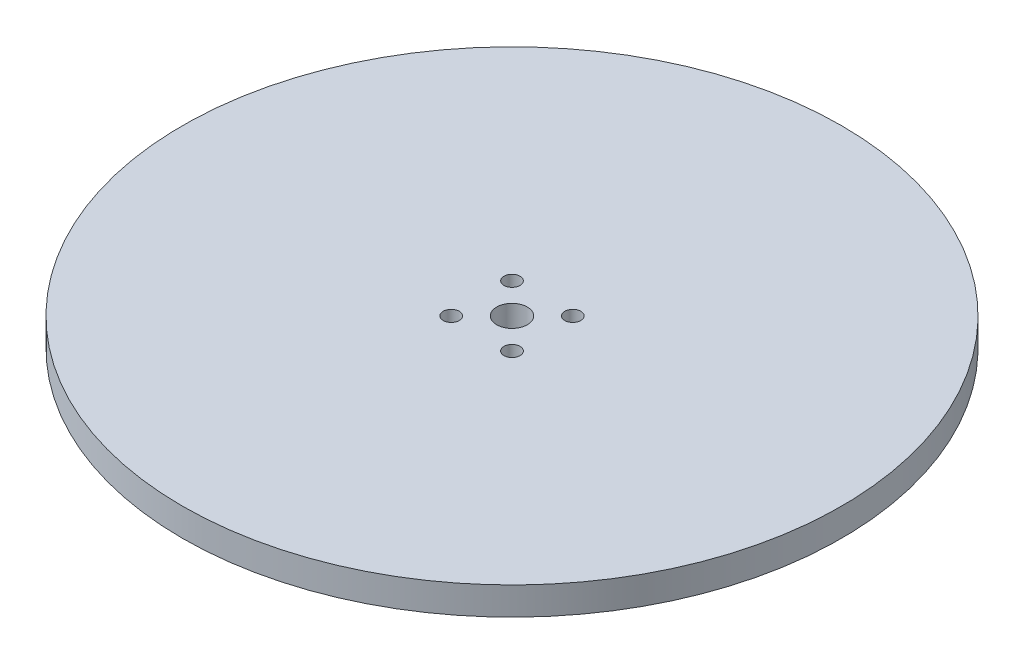
SolidWorks part; units mm, degrees
material "ABS"
ref_plane "Plan de face" through (0, 0, 0) normal (0, 0, 1) x (1, 0, 0)
ref_plane "Plan de dessus" through (0, 0, 0) normal (0, 1, 0) x (1, 0, 0)
ref_plane "Plan de droite" through (0, 0, 0) normal (1, 0, 0) x (0, 0, -1)
sketch "Esquisse1" plane through (0, 0, 0) normal (0, 1, 0) x (1, 0, 0)
  circle A0 centre (0, 0) radius 75
  dimension "D1" = 150
extrude "Boss.-Extru.1" add sketch "Esquisse1" along normal blind 6.35
sketch "Esquisse2" plane through (0, 6.35, 0) normal (0, 1, 0) x (1, 0, 0)
  circle A0 centre (0, 0) radius 3.5
  dimension "D1" = 7
extrude "Enlèv. mat.-Extru.1" cut sketch "Esquisse2" against normal up to surface (6.35 mm away) up to face at (0, 0, 75)
sketch "Sketch1" plane through (0, 0, 0) normal (0, -1, 0) x (1, 0, 0)
  circle A0 centre (-6.9148, 6.9148) radius 1.8288
  arc A2 (-6.9148, 8.6674) -> (-8.016, 5.5514) centre (-6.9148, 6.9148) ccw construction
  dimension "D1" = 3.6576
  dimension "D2" = 0
extrude "Cut-Extrude1" cut sketch "Sketch1" against normal up to surface (6.35 mm away) up to face at (0, 6.35, 3.5)
pattern_circular "CirPattern1" count 4 every 90 of "Cut-Extrude1"
